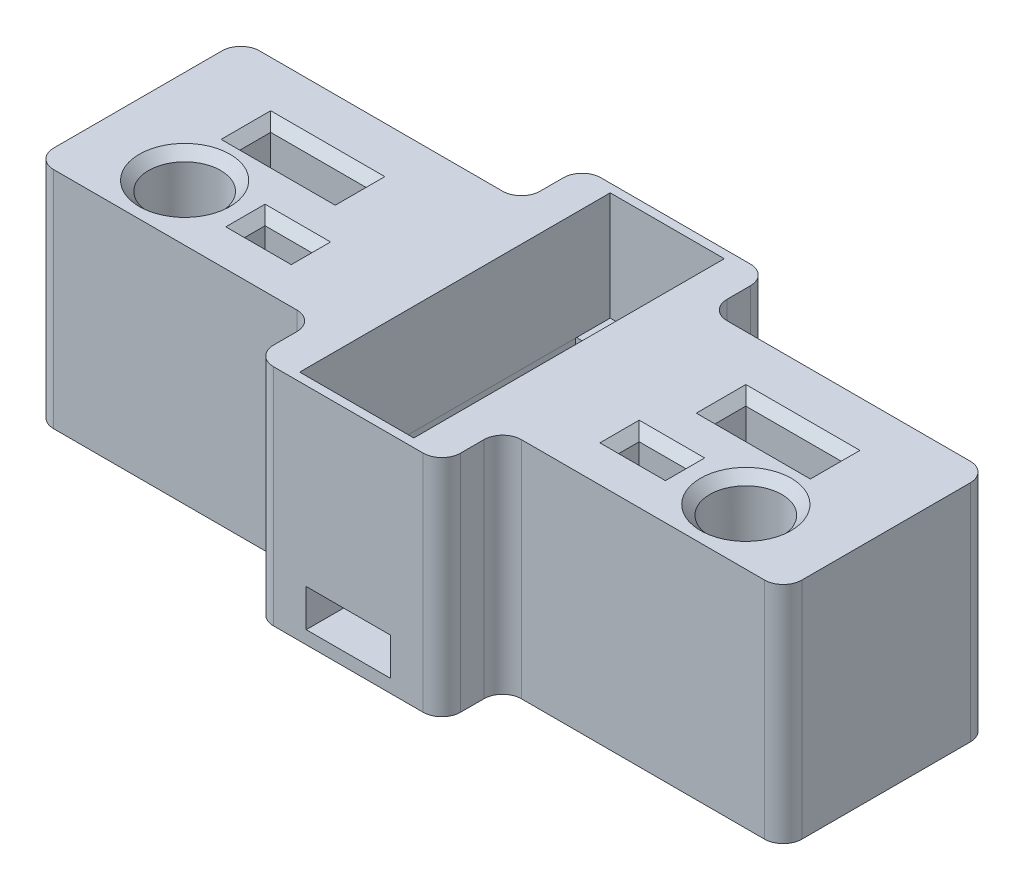
SolidWorks part; units mm, degrees
ref_plane "Front Plane" through (0, 0, 0) normal (0, 0, 1) x (1, 0, 0)
ref_plane "Top Plane" through (0, 0, 0) normal (0, 1, 0) x (1, 0, 0)
ref_plane "Right Plane" through (0, 0, 0) normal (1, 0, 0) x (0, 0, -1)
sketch "Sketch1" plane through (0, 0, 0) normal (0, 1, 0) x (1, 0, 0)
  line L1 (-40, -11) -> (40, -11)
  line L2 (-40, -11) -> (-40, 11)
  line L3 (-40, 11) -> (40, 11)
  line L4 (40, -11) -> (40, 11)
  line L5 (-40, -11) -> (40, 11) construction
  line L6 (-40, 11) -> (40, -11) construction
  point P0 (0, 0)
  dimension "D1" = 80
  dimension "D2" = 22
extrude "Boss-Extrude1" add sketch "Sketch1" along normal blind 24
sketch "Sketch2" plane through (0, 24, 0) normal (0, 1, 0) x (1, 0, 0)
  line L0 (0, 0) -> (0, -11) construction
  line L1 (-40, -11) -> (40, -11) construction
  circle A0 centre (-30, -5) radius 3.85
  circle A1 centre (30, -5) radius 3.85
  dimension "D1" = 7.7
  dimension "D2" = 7.7
  dimension "D3" = 60
  dimension "D4" = 30
  dimension "D5" = 6
  dimension "D6" = 6
extrude "Eyeshaft holes" cut sketch "Sketch2" against normal blind 15
sketch "Sketch5" plane through (0, 24, 0) normal (0, 1, 0) x (1, 0, 0)
  line L0 (-30, -5) -> (30, -5) construction
  line L2 (-22.5, -6.1) -> (-17.5, -6.1)
  line L3 (-22.5, -6.1) -> (-22.5, -3.9)
  line L4 (-22.5, -3.9) -> (-17.5, -3.9)
  line L5 (-17.5, -6.1) -> (-17.5, -3.9)
  line L6 (-22.5, -6.1) -> (-17.5, -3.9) construction
  line L7 (-22.5, -3.9) -> (-17.5, -6.1) construction
  line L8 (17.5, -6.1) -> (22.5, -6.1)
  line L9 (17.5, -6.1) -> (17.5, -3.9)
  line L10 (17.5, -3.9) -> (22.5, -3.9)
  line L11 (22.5, -6.1) -> (22.5, -3.9)
  line L12 (17.5, -6.1) -> (22.5, -3.9) construction
  line L13 (17.5, -3.9) -> (22.5, -6.1) construction
  point P4 (-20, -5)
  point P9 (20, -5)
  dimension "D1" = 2.2
  dimension "D2" = 5
  dimension "D3" = 5
  dimension "D4" = 2.2
  dimension "D5" = 10
  dimension "D6" = 10
extrude "Front leg holes" cut sketch "Sketch5" against normal blind 13
sketch "Sketch6" plane through (0, 0, 0) normal (0, 0, 1) x (1, 0, 0)
  line L0 (0, 24) -> (0, 0) construction
  line L1 (-40, 24) -> (40, 24) construction
  line L2 (-40, 0) -> (40, 0) construction
  line L4 (-10, 0) -> (10, 0)
  line L5 (-10, 0) -> (-10, 24)
  line L6 (-10, 24) -> (10, 24)
  line L7 (10, 0) -> (10, 24)
  line L8 (-10, 0) -> (10, 24) construction
  line L9 (-10, 24) -> (10, 0) construction
  point P6 (0, 12)
  dimension "D1" = 20
extrude "Servo block" add sketch "Sketch6" along normal mid plane 35
sketch "Sketch7" plane through (0, 24, 0) normal (0, 1, 0) x (1, 0, 0)
  line L1 (-30.85, 5.05) -> (-20.65, 5.05)
  line L2 (-30.85, 5.05) -> (-30.85, 1.75)
  line L3 (-30.85, 1.75) -> (-20.65, 1.75)
  line L4 (-20.65, 5.05) -> (-20.65, 1.75)
  line L5 (19.9, 5.1) -> (30.1, 5.1)
  line L6 (19.9, 5.1) -> (19.9, 1.8)
  line L7 (19.9, 1.8) -> (30.1, 1.8)
  line L8 (30.1, 5.1) -> (30.1, 1.8)
  line L10 (-40, 11) -> (-40, -11) construction
  line L11 (40, 11) -> (10, 11) construction
  line L12 (40, -11) -> (40, 11) construction
  circle A0 centre (-30, -5) radius 3.85 construction
  dimension "D1" = 3.3
  dimension "D2" = 10.2
  dimension "D3" = 10.2
  dimension "D4" = 3.3
  dimension "D5" = 10.05
  dimension "D6" = 5.9
  dimension "D7" = 9.15
  dimension "D8" = 9.9
extrude "Back Legs" cut sketch "Sketch7" against normal blind 13
fillet "Fillet1" radius 3 2 edges at (30, 9, 8.85) (-30, 9, 8.85)
sketch "Sketch8" plane through (0, 24, 0) normal (0, 1, 0) x (1, 0, 0)
  line L0 (30, -5) -> (-30, -5) construction
  circle A0 centre (0, -5) radius 2.7143
extrude "Cut-Extrude4" cut sketch "Sketch8" against normal blind 14
sketch "Sketch9" plane through (0, 24, 0) normal (0, 1, 0) x (1, 0, 0)
  line L1 (-6.1, 16.6) -> (6.1, 16.6)
  line L2 (-6.1, 16.6) -> (-6.1, -16.6)
  line L3 (-6.1, -16.6) -> (6.1, -16.6)
  line L4 (6.1, 16.6) -> (6.1, -16.6)
  circle A0 centre (0, -5) radius 2.7143 construction
  circle A1 centre (0, -5) radius 2.7143 construction
  dimension "D1" = 21.6
  dimension "D2" = 11.6
  dimension "D3" = 12.2
  dimension "D4" = 6.1
extrude "Servo arms1" cut sketch "Sketch9" against normal blind 11.6
fillet "Fillet2" radius 2 12 edges at (40, 12, 11) (40, 12, -11) (10, 12, -11) (10, 12, -17.5) (-10, 12, -17.5) (-10, 12, -11) (-40, 12, -11) (-40, 12, 11) (-10, 12, 11) (-10, 12, 17.5) (10, 12, 17.5) (10, 12, 11)
chamfer "Chamfer1" distance 1 angle 45 18 edges at (-17.5, 24, 5) (-20, 24, 3.9) (-22.5, 24, 5) (-20, 24, 6.1) (22.5, 24, 5) (20, 24, 6.1) (17.5, 24, 5) (20, 24, 3.9) (30.1, 24, -3.45) (25, 24, -1.8) (19.9, 24, -3.45) (25, 24, -5.1) (-20.65, 24, -3.4) (-25.75, 24, -1.75) (-30.85, 24, -3.4) (-25.75, 24, -5.05) (30, 24, 8.85) (-30, 24, 8.85)
sketch "Sketch14" plane through (0, 12.4, 0) normal (0, 1, 0) x (1, 0, 0)
  line L1 (-6.2, -12) -> (6.2, -12)
  line L2 (-6.2, -12) -> (-6.2, 13)
  line L3 (-6.2, 13) -> (6.2, 13)
  line L4 (6.2, -12) -> (6.2, 13)
  line L5 (-6.2, -12) -> (6.2, 13) construction
  line L6 (-6.2, 13) -> (6.2, -12) construction
  circle A1 centre (0, -5) radius 2.7143 construction
  point P0 (0.6239, -0.7578)
  dimension "D3" = 7
  dimension "D4" = 18
  dimension "D2" = 12.4
extrude "Cut-Extrude5" cut sketch "Sketch14" against normal blind 11
sketch "Sketch15" plane through (0, 0, 17.5) normal (0, 0, 1) x (1, 0, 0)
  line L0 (0, 0) -> (0, 24) construction
  line L1 (-8, 0) -> (8, 0) construction
  line L2 (8, 24) -> (-8, 24) construction
  line L4 (-4.5, 1.4) -> (4.5, 1.4)
  line L5 (-4.5, 1.4) -> (-4.5, 5.4)
  line L6 (-4.5, 5.4) -> (4.5, 5.4)
  line L7 (4.5, 1.4) -> (4.5, 5.4)
  line L8 (-4.5, 1.4) -> (4.5, 5.4) construction
  line L9 (-4.5, 5.4) -> (4.5, 1.4) construction
  point P6 (0, 3.4)
  dimension "D1" = 9
  dimension "D2" = 4
  dimension "D3" = 1.4
extrude "Cut-Extrude6" cut sketch "Sketch15" against normal up to surface (5.5 mm away) up to face at (0, 8.7333, 12)
sketch "Sketch16" plane through (0, 12.4, 0) normal (0, 1, 0) x (1, 0, 0)
  line L0 (-6.1, -12) -> (6.1, -12) construction
  line L1 (-2.5, -12.5) -> (2.5, -12.5)
  line L2 (-2.5, -12.5) -> (-2.5, -11.5)
  line L3 (-2.5, -11.5) -> (2.5, -11.5)
  line L4 (2.5, -12.5) -> (2.5, -11.5)
  line L5 (-2.5, -12.5) -> (2.5, -11.5) construction
  line L6 (-2.5, -11.5) -> (2.5, -12.5) construction
  point P0 (0, -12)
  dimension "D1" = 5
  dimension "D2" = 1
extrude "Cut-Extrude7" cut sketch "Sketch16" against normal up to surface (11 mm away) up to face at (0, 1.4, 7.125)
sketch "Sketch13" plane through (0, 12.4, 0) normal (0, 1, 0) x (1, 0, 0)
  line L1 (6.1, 13) -> (6.1, 16.6) construction
  line L2 (6.1, 13) -> (-6.1, 13) construction
  line L4 (6.1, -16.6) -> (6.1, -12) construction
  line L5 (-2.5, -12.5) -> (2.5, -12.5) construction
  circle A0 centre (0.1, 15) radius 0.5
  circle A1 centre (0.1, -14.5) radius 0.5
  dimension "D2" = 6
  dimension "D3" = 1
  dimension "D4" = 1
  dimension "D1" = 2
  dimension "D5" = 2
  dimension "D6" = 6
extrude "Servo Screw Holes" cut sketch "Sketch13" against normal blind 2
fillet "Fillet3" radius 2 3 edges at (0, 5.4, 12.5) (2.5, 5.4, 12.25) (-2.5, 5.4, 12.25)
